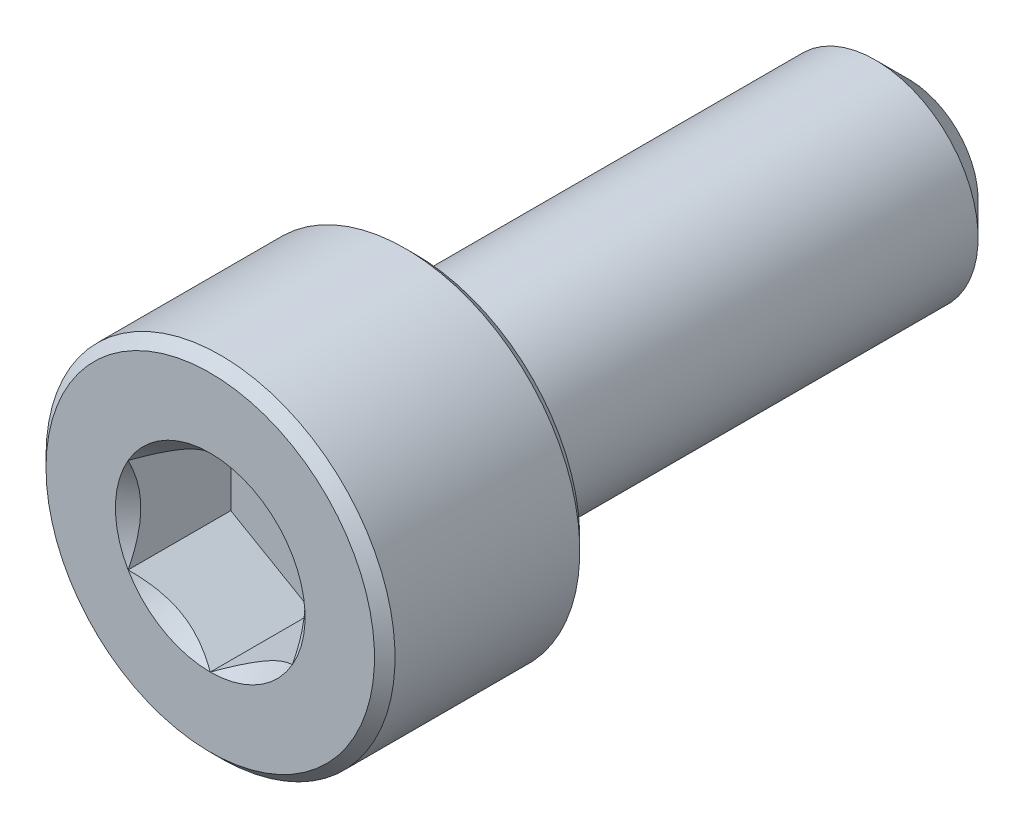
SolidWorks part; units mm, degrees
ref_plane "Front Plane" through (0, 0, 0) normal (0, 0, 1) x (1, 0, 0)
ref_plane "Top Plane" through (0, 0, 0) normal (0, 1, 0) x (1, 0, 0)
ref_plane "Right Plane" through (0, 0, 0) normal (1, 0, 0) x (0, 0, -1)
sketch "Sketch1" plane through (0, 0, 0) normal (1, 0, 0) x (0, 0, -1)
  line L0 (-8.5, 0) -> (8.5, 0) construction
  line L1 (8.5, 0) -> (8.5, 1.7) construction
  line L2 (8.5, 1.7) -> (7.7, 2.5) construction
  line L3 (7.7, 2.5) -> (-3.5, 2.5) construction
  line L5 (-3.5, 2.5) -> (-3.5, 4.25) construction
  line L6 (-3.5, 4.25) -> (-8.5, 4.25) construction
  line L7 (-8.5, 4.25) -> (-8.5, 0) construction
  line L8 (8.5, 1.7) -> (8.5, 2.5) construction
  line L9 (8.45, 2.5866) -> (8.85, 1.8938) construction
  line L10 (8.85, 1.8938) -> (9.25, 2.5866) construction
  line L11 (9.25, 2.5866) -> (8.45, 2.5866) construction
  line L12 (8.85, 2.5866) -> (8.85, 2.5) construction
  line L13 (8.85, 1.8938) -> (8.85, 1.9804) construction
  line L14 (8.8, 1.9804) -> (8.9, 1.9804) construction
  line L15 (8.5, 2.5) -> (9.2, 2.5) construction
  line L16 (8.475, 2.5433) -> (9.225, 2.5433) construction
  line L17 (8.5, 0) -> (8.5, -2.5) construction
  line L18 (-3.75, 4.25) -> (-3.5, 4) construction
  line L19 (-8.25, 4.25) -> (-8.5, 4) construction
  point P0 (-8.5, 2)
  point P3 (5.7, 2.5)
  point P4 (0, 0)
  point P22 (8.85, 1.9804)
  point P24 (-3.5, 2.5)
  point P25 (8.85, 2.5)
  point P28 (8.85, 2.5433)
  point P29 (5.7, -2.5)
  point P31 (-6, 4.25)
  point P37 (-4.375, 4.25)
  point P38 (-8.125, 4.25)
  point P41 (-6, 0)
  dimension "head height" = 5
  dimension "D1" = 45
  dimension "Head Diameter" = 8.5
  dimension "Thread Size" = 5
  dimension "drive size" = 4
  dimension "Thread Pitch" = 0.8
  dimension "D2" = 0.1
  dimension "D3" = 0.8
  dimension "D4" = 2.8
  dimension "D7" = 0.25
  dimension "D8" = 0.25
  dimension "D9" = 0.25
  dimension "D10" = 0.125
  dimension "D11" = 0.625
  dimension "length" = 12
  dimension "Drive Depth" = 2.5
sketch "Sketch2" plane through (0, 0, 0) normal (1, 0, 0) x (0, 0, -1)
  line L1 (-8.25, 4.25) -> (-3.75, 4.25)
  line L4 (7.7, 2.5) -> (8.5, 1.7)
  line L5 (8.5, 1.7) -> (8.5, 0)
  line L6 (-3.75, 4.25) -> (-3.5, 4) construction
  line L7 (8.5, 0) -> (-8.5, 0)
  line L8 (-8.25, 4.25) -> (-8.5, 4) construction
  line L9 (-3.75, 4.25) -> (-3.5, 4)
  line L10 (-8.25, 4.25) -> (-8.5, 4)
  line L11 (-8.5, 4) -> (-8.5, 0)
  line L12 (-3.5, 4) -> (-3.5, 2.5)
  line L13 (-3.5, 2.5) -> (7.7, 2.5)
revolve "Revolve1" add sketch "Sketch2" angle 360 about L7
sketch "Sketch3" plane through (0, 0, 8.5) normal (0, 0, 1) x (1, 0, 0)
  line L1 (0, 2.3094) -> (-2, 1.1547)
  line L2 (-2, 1.1547) -> (-2, -1.1547)
  line L3 (-2, -1.1547) -> (0, -2.3094)
  line L4 (0, -2.3094) -> (2, -1.1547)
  line L5 (2, -1.1547) -> (2, 1.1547)
  line L6 (2, 1.1547) -> (0, 2.3094)
  circle A0 centre (0, 0) radius 2 construction
  dimension "D1" = 4
extrude "Cut-Extrude1" cut sketch "Sketch3" against normal up to vertex (2.5 mm away) up to point (0, 0, 6)
sketch "Sketch4" plane through (0, 0, 8.5) normal (0, 0, 1) x (1, 0, 0)
  circle A0 centre (0, 0) radius 2.3094
extrude "Cut-Extrude2" cut sketch "Sketch4" against normal blind 0.5 draft 45
ref_plane "Plane1" [suppressed] through (0, 0, 3.5) normal (0, 0, 1) x (1, 0, 0)
split "Split1" [suppressed] bodies to split 106
sketch "Sketch6" [suppressed] plane through (0, 0, -8.5) normal (0, 0, -1) x (-1, 0, 0)
  circle A0 centre (0, 0) radius 2.5
curve "Helix/Spiral1" [suppressed] pitch 0.8 height 12.8 turns 16
sketch "Sketch7" [suppressed] plane through (0, 0, 0) normal (1, 0, 0) x (0, 0, -1)
  line L0 (8.475, 2.5433) -> (9.225, 2.5433)
  line L1 (9.225, 2.5433) -> (8.9, 1.9804)
  line L2 (8.9, 1.9804) -> (8.8, 1.9804)
  line L3 (8.8, 1.9804) -> (8.475, 2.5433)
sweep "Cut-Sweep1" [suppressed] cut profiles "Sketch7" path "Helix/Spiral1"
sketch "Sketch8" [suppressed] plane through (0, 0, 3.5) normal (0, 0, -1) x (-1, 0, 0)
  circle A0 centre (0, 0) radius 2.5
extrude "Boss-Extrude1" [suppressed] add sketch "Sketch8" along normal through all draft 45
ref_plane "Plane2" [suppressed] through (0, 0, 6) normal (0, 0, 1) x (1, 0, 0)
sketch "Sketch9" [suppressed] plane through (0, 0, 6) normal (0, 0, 1) x (1, 0, 0)
  line L0 (0, 4.1331) -> (0.1113, 4.2485)
  line L1 (0, 4.1331) -> (-0.1113, 4.2485)
  line L2 (0, 4.25) -> (0, 0) construction
  line L3 (-0.1113, 4.2485) -> (0, 0) construction
  line L4 (0, 0) -> (0.1113, 4.2485) construction
  arc A0 (0.1113, 4.2485) -> (-0.1113, 4.2485) centre (0, 0) ccw
  circle A1 centre (0, 0) radius 4.1331 construction
  dimension "D1" = 8.5
  dimension "D2" = 8.2662
  dimension "D3" = 3
extrude "Cut-Extrude4" [suppressed] cut sketch "Sketch9" against normal up to vertex and the other way up to vertex
pattern_circular "CirPattern2" [suppressed] count 96 over 360 about axis through (0, 0, 8.5) along (0, 0, -1) of bodies 113
equation "\"D2@Sketch1\" = \"Thread Pitch@Sketch1\" / 8"
equation "\"D3@Sketch1\" = \"Thread Pitch@Sketch1\""
equation "\"D3@Helix/Spiral1\" = \"length@Sketch1\" + \"Thread Pitch@Sketch1\""
equation "\"D4@Helix/Spiral1\" = \"Thread Pitch@Sketch1\""
equation "\"D4@Sketch1\" = \"Thread Pitch@Sketch1\" * 3.5"
equation "\"D7@Sketch1\"=\"head height@Sketch1\"*.05"
equation "\"D8@Sketch1\"=\"D7@Sketch1\""
equation "\"D9@Sketch1\"=\"D7@Sketch1\""
equation "\"D10@Sketch1\"=\"D7@Sketch1\"/2"
equation "\"D11@Sketch1\"=\"D10@Sketch1\"*5"
equation "\"D1@CirPattern2\"=( 360 / \"D3@Sketch9\" )*0.8"
equation "\"D1@Sketch3\" = \"drive size@Sketch1\""
equation "\"D2@Sketch9\"=\"Head Diameter@Sketch1\" * 0.9725"
